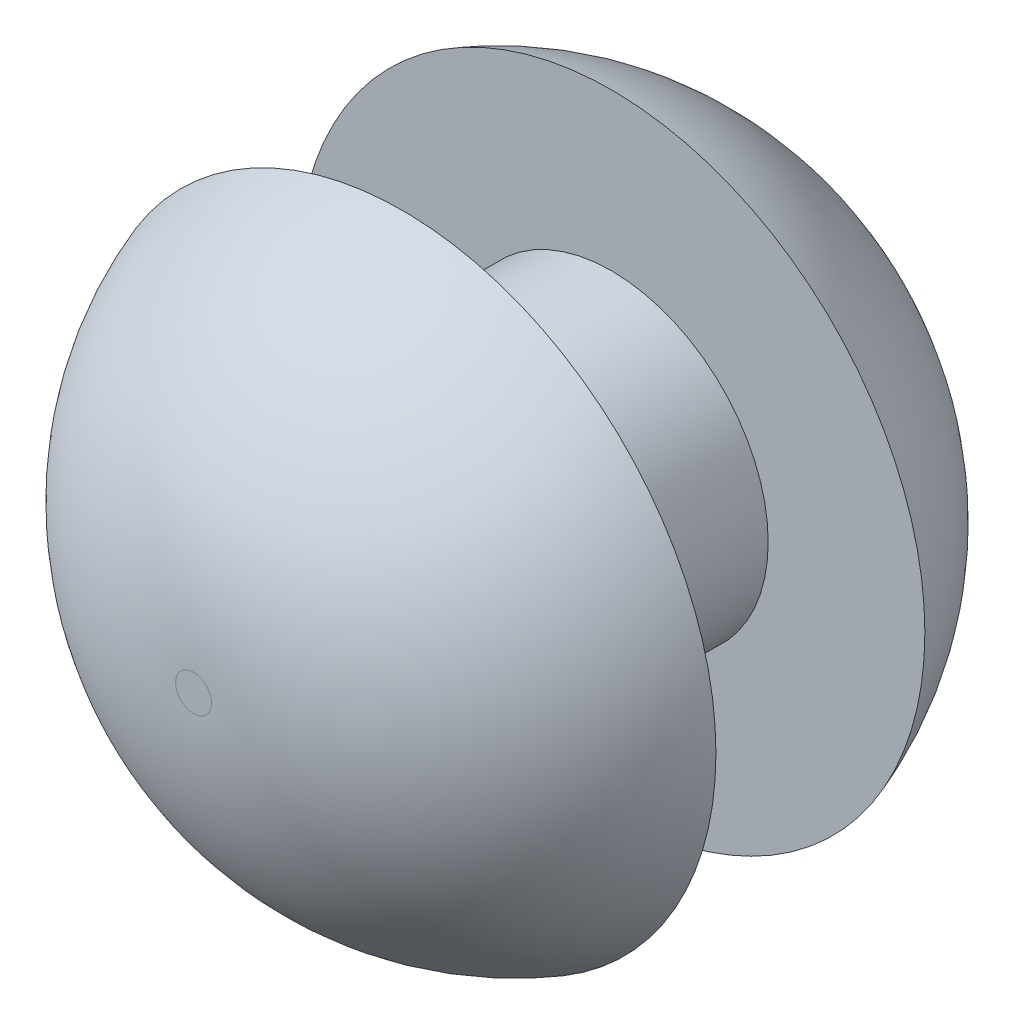
SolidWorks part; units mm, degrees
material "AISI 304"
ref_plane "Plano frontal" through (0, 0, 0) normal (0, 0, 1) x (1, 0, 0)
ref_plane "Plano superior" through (0, 0, 0) normal (0, 1, 0) x (1, 0, 0)
ref_plane "Plano direito" through (0, 0, 0) normal (1, 0, 0) x (0, 0, -1)
sketch "Esboço1" plane through (0, 0, 0) normal (0, 0, 1) x (1, 0, 0)
  circle A0 centre (0, 0) radius 0.15
  dimension "D1" = 0.3
extrude "Ressalto-extrusão1" add sketch "Esboço1" along normal mid plane 0.2
sketch "Esboço2" plane through (0, 0, 0.1) normal (0, 0, 1) x (1, 0, 0)
  circle A0 centre (0, 0) radius 0.3
  dimension "D1" = 0.6
extrude "Ressalto-extrusão2" add sketch "Esboço2" along normal blind 0.2
fillet "Filete1" radius 0.3 1 edges at (0.3, 0, 0.3)
mirror "Espelhar2" about plane through (0, 0, 0) normal (0, 0, 1) of bodies 102
